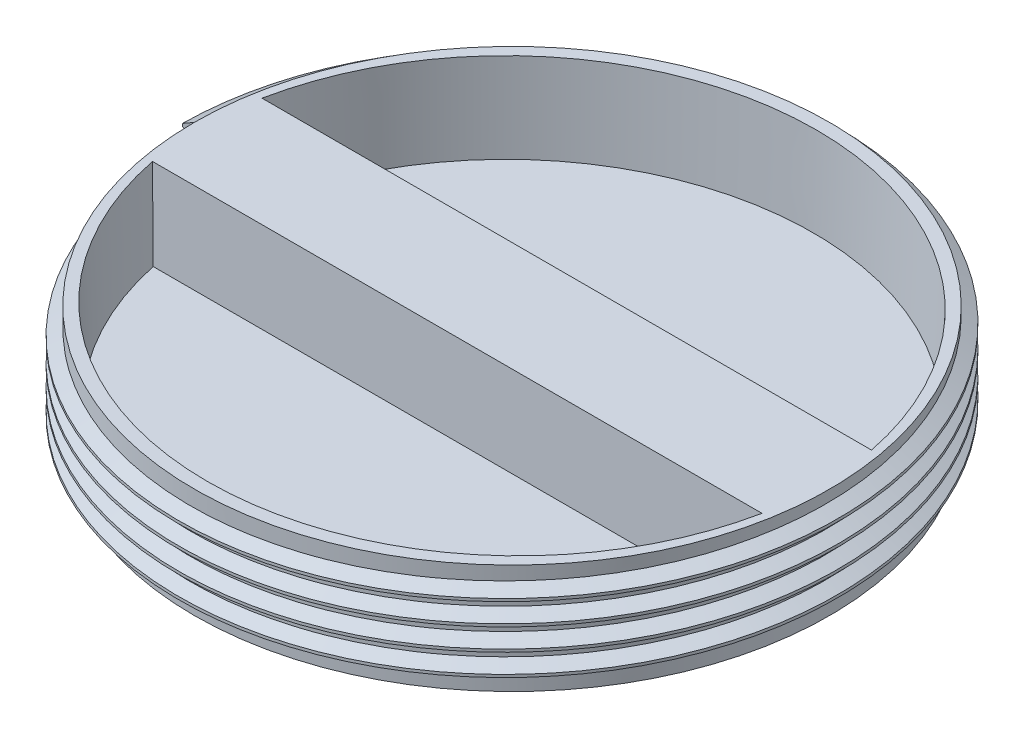
SolidWorks part; units mm, degrees
ref_plane "Front Plane" through (0, 0, 0) normal (0, 0, 1) x (1, 0, 0)
ref_plane "Top Plane" through (0, 0, 0) normal (0, 1, 0) x (1, 0, 0)
ref_plane "Right Plane" through (0, 0, 0) normal (1, 0, 0) x (0, 0, -1)
sketch "Sketch1" plane through (0, 0, 0) normal (0, 1, 0) x (1, 0, 0)
  circle A0 centre (0, 0) radius 29
  dimension "D1" = 58
extrude "Boss-Extrude2" add sketch "Sketch1" along normal blind 10
ref_plane "Plane1" through (0, 0, 45) normal (0, 0, 1) x (1, 0, 0)
thread "Thread1" pitch 2 method extrude profile "Thread Profile1" start angle 0, offset 0, length 8, pitch 2, diameter 58
ref_plane "Plane2" through (-29, 10, 0) normal (0, 0, 1) x (-1, 0, 0)
sketch "Thread Profile1" plane through (-29, 10, 0) normal (0, 0, 1) x (-1, 0, 0)
  line L0 (0, 0) -> (0, 2) construction
  line L1 (0, 0) -> (1.0825, 0.625)
  line L2 (1.0825, 0.625) -> (1.0825, 0.875)
  line L3 (1.0825, 0.875) -> (0, 1.5)
  line L4 (1.0825, 0.75) -> (0, 0.75) construction
  line L11 (0, 0) -> (0, 1.5)
  point P2 (0, 0)
  dimension "Pitch" = 2
  dimension "Profile_Angle" = 60
  dimension "Profile_Land" = 0.25
  dimension "Profile_Height" = 1.0825
ref_plane "Plane3" through (0, 0, 10) normal (0, 0, 1) x (1, 0, 0)
sketch "Sketch5" plane through (0, 10, 0) normal (0, 1, 0) x (1, 0, 0)
  line L0 (0, 0) -> (29, 0) construction
  line L1 (27.8215, 5) -> (-27.8215, 5) construction
  line L2 (27.8215, 5) -> (27.8215, -5) construction
  line L3 (27.8215, -5) -> (-27.8215, -5)
  line L4 (-27.8215, 5) -> (-27.8215, -5) construction
  line L5 (27.8215, 5) -> (-27.8215, -5) construction
  line L6 (27.8215, -5) -> (-27.8215, 5) construction
  arc A0 (-27.8215, -5) -> (27.8215, -5) centre (0, 0.576) ccw
  circle A1 centre (0, 0) radius 29 construction
  point P0 (0, 0)
  dimension "D1" = 10
  dimension "D2" = 5
  dimension "D3" = 5
extrude "Cut-Extrude2" cut sketch "Sketch5" against normal blind 8 draft 2
mirror "Mirror1" about plane through (0, 0, 0) normal (0, 0, 1) of "Cut-Extrude2"
